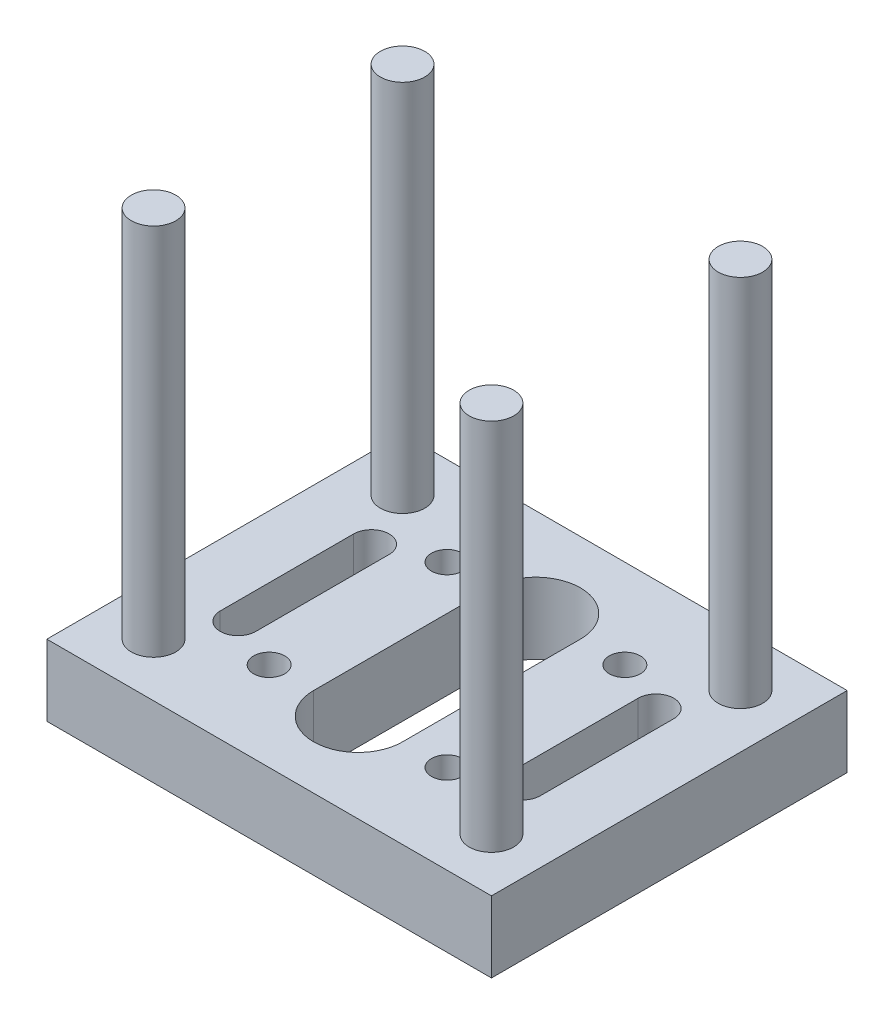
SolidWorks part; units mm, degrees
ref_plane "Front Plane" through (0, 0, 0) normal (0, 0, 1) x (1, 0, 0)
ref_plane "Top Plane" through (0, 0, 0) normal (0, 1, 0) x (1, 0, 0)
ref_plane "Right Plane" through (0, 0, 0) normal (1, 0, 0) x (0, 0, -1)
sketch "Sketch1" plane through (0, 0, 0) normal (0, 1, 0) x (1, 0, 0)
  line L0 (0, 24.2088) -> (0, -20) construction
  line L1 (-25, -20) -> (25, -20)
  line L2 (-25, -20) -> (-25, 20)
  line L3 (-25, 20) -> (25, 20)
  line L4 (25, -20) -> (25, 20)
  line L5 (-25, -20) -> (25, 20) construction
  line L6 (-25, 20) -> (25, -20) construction
  line L7 (-25, 0) -> (25, 0) construction
  line L8 (-16, 7.5) -> (-16, -7.5) construction
  line L9 (-14, 7.5) -> (-14, -7.5)
  line L10 (-18, 7.5) -> (-18, -7.5)
  line L11 (16, 7.5) -> (16, -7.5) construction
  line L12 (14, 7.5) -> (14, -7.5)
  line L13 (18, 7.5) -> (18, -7.5)
  line L14 (0, 10) -> (0, -10) construction
  line L15 (5, 10) -> (5, -10)
  line L16 (-5, 10) -> (-5, -10)
  circle A0 centre (-19, 14) radius 2.5
  circle A1 centre (-19, -14) radius 2.5
  circle A2 centre (19, 14) radius 2.5
  circle A3 centre (19, -14) radius 2.5
  arc A4 (-14, 7.5) -> (-18, 7.5) centre (-16, 7.5) ccw
  arc A5 (-18, -7.5) -> (-14, -7.5) centre (-16, -7.5) ccw
  arc A6 (14, 7.5) -> (18, 7.5) centre (16, 7.5) cw
  arc A7 (18, -7.5) -> (14, -7.5) centre (16, -7.5) cw
  arc A8 (5, 10) -> (-5, 10) centre (0, 10) ccw
  arc A9 (-5, -10) -> (5, -10) centre (0, -10) ccw
  circle A10 centre (-10, 10) radius 1.75
  circle A11 centre (-10, -10) radius 1.75
  circle A12 centre (10, -10) radius 1.75
  circle A13 centre (10, 10) radius 1.75
  point P0 (0, 0)
  point P12 (-16, 0)
  point P25 (0, 0)
  point P28 (16, 0)
  dimension "D5" = 5
  dimension "D11" = 3.5
  dimension "D1" = 50
  dimension "D2" = 40
  dimension "D3" = 6
  dimension "D4" = 6
  dimension "D6" = 4
  dimension "D7" = 7
  dimension "D8" = 15
  dimension "D9" = 10
  dimension "D10" = 20
  dimension "D12" = 10
  dimension "D13" = 5
extrude "Main Structure" add sketch "Sketch1" along normal blind 8
extrude "Boss-Extrude2" add sketch "Sketch1<3>" along normal blind 3 contours A0 | A2 | A1 | A3 region at (-19, 0, -14) region at (-19, 0, 14) region at (19, 0, -14) region at (19, 0, 14)
sketch "Sketch1<3>" plane through (0, 0, 0) normal (0, 1, 0) x (1, 0, 0) same geometry as "Sketch1"
extrude "Shafts" add sketch "Sketch1<4>" along normal blind 50 contours A1 | A3 | A2 | A0 region at (-19, 0, -14) region at (-19, 0, 14) region at (19, 0, -14) region at (19, 0, 14)
sketch "Sketch1<4>" plane through (0, 0, 0) normal (0, 1, 0) x (1, 0, 0) same geometry as "Sketch1"
